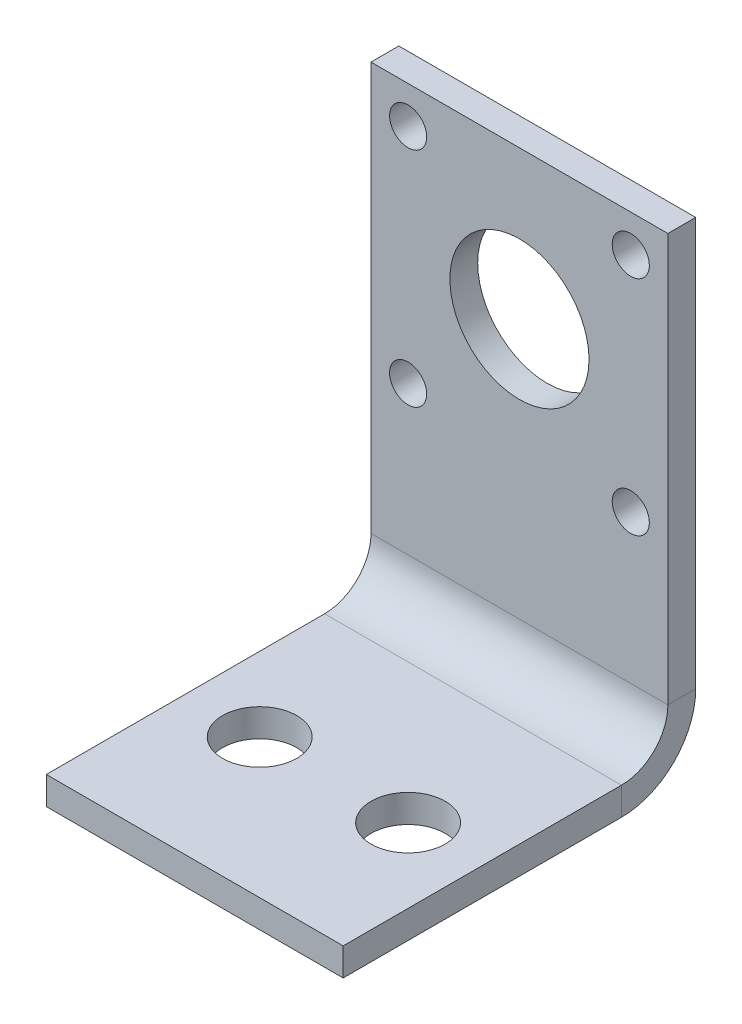
SolidWorks part; units mm, degrees
note: The reader was unsure of these and kept them because the rebuilt part matched: flange length of "Edge-Flange1".
material "Ductile Iron"
ref_plane "Front Plane" through (0, 0, 0) normal (0, 0, 1) x (1, 0, 0)
ref_plane "Top Plane" through (0, 0, 0) normal (0, 1, 0) x (1, 0, 0)
ref_plane "Right Plane" through (0, 0, 0) normal (1, 0, 0) x (0, 0, -1)
sketch "Sketch5" plane through (0, 0, 0) normal (0, 1, 0) x (1, 0, 0)
  line L1 (-16, -15) -> (16, -15)
  line L2 (-16, -15) -> (-16, 15)
  line L3 (-16, 15) -> (16, 15)
  line L4 (16, -15) -> (16, 15)
  line L5 (-16, -15) -> (16, 15) construction
  line L6 (-16, 15) -> (16, -15) construction
  point P0 (0, 0)
  dimension "D1" = 30
  dimension "D2" = 32
base flange "Base-Flange1" sketch "Sketch5" thickness 3 reverse thickness direction yes parameters "D1"=10
edge flange "Edge-Flange1" sketch "Sketch12" flange angle 90 flange length 52 flange position bend outside bend radius 5 thickness 3 relief rectangular parameters "D6"=10
sketch "Sketch12" plane through (0, 3, -15) normal (0, 0, -1) x (-1, 0, 0)
  line L2 (-16, 0) -> (-16, 49)
  line L3 (-16, 49) -> (16, 49)
  line L4 (16, 49) -> (16, 0)
  line L11 (-16, 0) -> (16, 0) construction
  line L12 (-16, 0) -> (16, 0)
bend "EdgeBend1" bend radius 5 bend angle 90 parameters "D5"=1
sketch "Sketch13" plane through (0, 3, 0) normal (0, 1, 0) x (1, 0, 0)
  line L0 (-16, -15) -> (16, -15) construction
  circle A0 centre (-8, 0) radius 4
  circle A1 centre (8, 0) radius 4
  dimension "D1" = 8
  dimension "D4" = 8
  dimension "D2" = 8
  dimension "D3" = 8
  dimension "D5" = 15
  dimension "D6" = 15
extrude "Cut-Extrude1" cut sketch "Sketch13" against normal blind 10 normal cut yes
sketch "Sketch14" plane through (0, 0, -20) normal (0, 0, 1) x (1, 0, 0)
  line L0 (0, 3) -> (0, 36) construction
  line L1 (16, 3) -> (-16, 3) construction
  line L2 (-16, 36) -> (16, 36) construction
  line L3 (16, 52) -> (16, 8) construction
  line L4 (-16, 8) -> (-16, 52) construction
  circle A0 centre (0, 36) radius 7.5
  circle A1 centre (-12, 48) radius 2
  circle A2 centre (12, 48) radius 2
  circle A3 centre (12, 24) radius 2
  circle A4 centre (-12, 24) radius 2
  dimension "D2" = 15
  dimension "D3" = 4
  dimension "D1" = 33
  dimension "D4" = 12
  dimension "D5" = 12
extrude "Cut-Extrude2" cut sketch "Sketch14" against normal blind 10 normal cut yes
sketch "Bend-Lines1" [suppressed] plane through (0, 0, 0) normal (0, 1, 0) x (1, 0, 0)
sketch "Bounding-Box1" [suppressed] plane through (0, 0, 0) normal (0, 1, 0) x (1, 0, 0)
sheet metal parameters "Sheet-Metal4" thickness 3 parameters "D1"=10
flat pattern "Flat-Pattern4" [suppressed]
sketch "Bend-Lines2" plane through (0, 0, 0) normal (0, 1, 0) x (1, 0, 0)
sketch3d "Bounding-Box2" [suppressed]
  line L0 (16, 15, 0) -> (-16, 15, 0) construction
  line L1 (16, -15, 0) -> (-16, -15, 0) construction
  line L2 (16, 15, 0) -> (16, -15, 0) construction
  line L3 (-16, 15, 0) -> (-16, -15, 0) construction
sheet metal parameters "Sheet-Metal5" thickness 3 parameters "D1"=10
flat pattern "Flat-Pattern4" [suppressed]
sketch "Bend-Lines2" plane through (0, 0, 0) normal (0, -1, 0) x (-1, 0, 0)
  line L0 (16, 20.1051) -> (-16, 20.1051) construction
  line L1 (16, 20.1051) -> (-16, 20.1051) construction
sketch3d "Bounding-Box2" [suppressed]
  line L0 (16, -15, 0) -> (16, 57.2102, 0) construction
  line L1 (-16, -15, 0) -> (-16, 57.2102, 0) construction
  line L2 (16, -15, 0) -> (-16, -15, 0) construction
  line L3 (16, 57.2102, 0) -> (-16, 57.2102, 0) construction
bend of the flat pattern "Flatten-<EdgeBend1>1"
sheet metal parameters "Sheet-Metal6" thickness 3 parameters "D1"=10
flat pattern "Flat-Pattern4" [suppressed]
sketch "Bend-Lines2" plane through (0, 0, 0) normal (0, -1, 0) x (-1, 0, 0)
  line L0 (16, 20.1051) -> (-16, 20.1051) construction
  line L1 (16, 20.1051) -> (-16, 20.1051) construction
sketch3d "Bounding-Box2" [suppressed]
  line L0 (16, -15, 0) -> (16, 72.2102, 0) construction
  line L1 (-16, -15, 0) -> (-16, 72.2102, 0) construction
  line L2 (16, -15, 0) -> (-16, -15, 0) construction
  line L3 (16, 72.2102, 0) -> (-16, 72.2102, 0) construction
sketch "Sketch14-1" [suppressed] plane through (0, 3, -17.2102) normal (0, 1, 0) x (1, 0, 0)
  line L0 (0, 3) -> (0, 39) construction
  dimension "D1" = 36
bend of the flat pattern "Flatten-<EdgeBend1>1"
sheet metal parameters "Sheet-Metal7" thickness 3 parameters "D1"=10
flat pattern "Flat-Pattern4" [suppressed]
sketch "Bend-Lines2" plane through (0, 0, 0) normal (0, -1, 0) x (-1, 0, 0)
  line L0 (16, 20.1051) -> (-16, 20.1051) construction
  line L1 (16, 20.1051) -> (-16, 20.1051) construction
sketch3d "Bounding-Box2" [suppressed]
  line L0 (16, -15, 0) -> (16, 69.2102, 0) construction
  line L1 (-16, -15, 0) -> (-16, 69.2102, 0) construction
  line L2 (16, -15, 0) -> (-16, -15, 0) construction
  line L3 (16, 69.2102, 0) -> (-16, 69.2102, 0) construction
bend of the flat pattern "Flatten-<EdgeBend1>1"
sketch "Sketch14-1" plane through (0, 3, -17.2102) normal (0, 1, 0) x (1, 0, 0)
  line L0 (0, 3) -> (0, 36) construction
  line L2 (-16, 36) -> (16, 36) construction
  circle A0 centre (0, 36) radius 7.5
  circle A1 centre (-12, 48) radius 2
  circle A2 centre (12, 48) radius 2
  circle A3 centre (12, 24) radius 2
  circle A4 centre (-12, 24) radius 2
  dimension "D2" = 15
  dimension "D3" = 4
  dimension "D1" = 33
  dimension "D4" = 12
  dimension "D5" = 12
